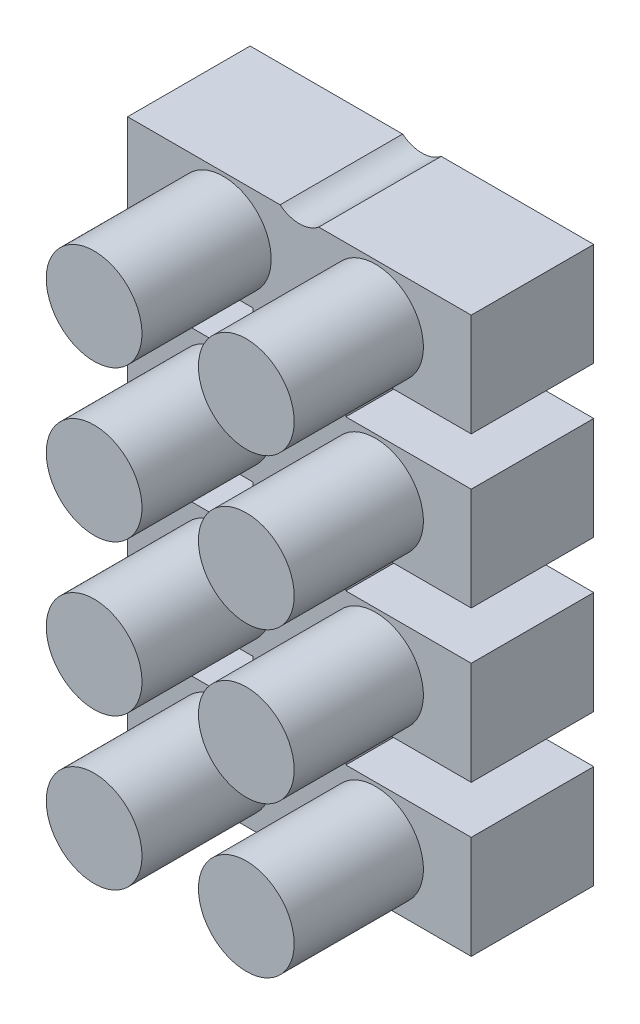
SolidWorks part; units mm, degrees
ref_plane "Front Plane" through (0, 0, 0) normal (0, 0, 1) x (1, 0, 0)
ref_plane "Top Plane" through (0, 0, 0) normal (0, 1, 0) x (1, 0, 0)
ref_plane "Right Plane" through (0, 0, 0) normal (1, 0, 0) x (0, 0, -1)
sketch "Sketch1" plane through (0, 0, 0) normal (0, 0, 1) x (1, 0, 0)
  line L1 (-9.1186, -6.7437) -> (9.1186, -6.7437)
  line L2 (-9.1186, -6.7437) -> (-9.1186, 6.7437)
  line L3 (-9.1186, 6.7437) -> (9.1186, 6.7437)
  line L4 (9.1186, -6.7437) -> (9.1186, 6.7437)
  line L5 (-9.1186, -6.7437) -> (9.1186, 6.7437) construction
  line L6 (-9.1186, 6.7437) -> (9.1186, -6.7437) construction
  point P0 (0, 0)
  dimension "D1" = 13.4874
  dimension "D2" = 18.2372
extrude "Boss-Extrude1" add sketch "Sketch1" along normal blind 6.5024
sketch "Sketch2" plane through (0, 0, 6.5024) normal (0, 0, 1) x (1, 0, 0)
  line L0 (9.1186, -6.7437) -> (9.1186, 6.7437) construction
  line L1 (9.1186, 1.27) -> (2.4638, 1.27)
  line L2 (9.1186, 1.27) -> (9.1186, -1.27)
  line L3 (9.1186, -1.27) -> (2.4638, -1.27)
  line L4 (2.4638, 1.27) -> (2.4638, -1.27)
  line L5 (2.4638, 0) -> (0, 0) construction
  dimension "D1" = 2.54
  dimension "D2" = 6.6548
extrude "Cut-Extrude1" cut sketch "Sketch2" against normal through all
sketch "Sketch5" plane through (0, 0, 6.5024) normal (0, 0, 1) x (1, 0, 0)
  line L0 (4.0386, -4.0069) -> (9.1186, -4.0068) construction
  line L2 (9.1186, -6.7437) -> (9.1186, -1.27) construction
  circle A0 centre (4.0386, -4.0069) radius 2.54
  dimension "D1" = 5.08
  dimension "D2" = 5.08
extrude "Boss-Extrude2" add sketch "Sketch5" along normal blind 6.858
sketch "Sketch6" plane through (0, 0, 6.5024) normal (0, 0, 1) x (1, 0, 0)
  line L1 (9.1186, 1.27) -> (-9.1186, 1.27)
  line L2 (9.1186, 1.27) -> (9.1186, 6.7437)
  line L3 (9.1186, 6.7437) -> (-9.1186, 6.7437)
  line L4 (-9.1186, 1.27) -> (-9.1186, 6.7437)
extrude "Cut-Extrude2" cut sketch "Sketch6" against normal through all
hole_wizard "#4 Clearance Hole1" positions "Sketch4" profile "Sketch3" hole size "#4" standard "ANSI Inch" end condition through all
sketch "Sketch4" plane through (0, 0, 6.5024) normal (0, 0, 1) x (1, 0, 0)
  point P0 (0, 0)
sketch "Sketch3" plane through (0, 0, 6.5024) normal (1, 0, 0) x (0, -1, 0)
  line L0 (0, 0) -> (0, 6.5024)
  line L1 (0, 6.5024) -> (1.6319, 6.5024)
  line L2 (1.6319, 6.5024) -> (1.6319, 0)
  line L5 (1.6319, 0) -> (0, 0)
  line L11 (0, -6.35) -> (0, 107.95) construction
  dimension "Thru Hole Dia." = 3.2639
  dimension "Thru Hole Depth" = 6.5024
mirror "Mirror4" about plane through (0, 0, 0) normal (1, 0, 0) of "Cut-Extrude1", "Boss-Extrude2"
pattern_linear "LPattern1" count 4 spacing 8.001 along (0, 1, 0) of "Boss-Extrude1", "Cut-Extrude1", "#4 Clearance Hole1", "Boss-Extrude2", "Mirror4"
sketch "Sketch7" plane through (0, 0, 6.5024) normal (0, 0, 1) x (1, 0, 0)
  line L1 (-9.1186, 30.7467) -> (9.1186, 30.7467)
  line L2 (-9.1186, 30.7467) -> (-9.1186, 22.733)
  line L3 (-9.1186, 22.733) -> (9.1186, 22.733)
  line L4 (9.1186, 30.7467) -> (9.1186, 22.733)
extrude "Cut-Extrude3" cut sketch "Sketch7" against normal through all
